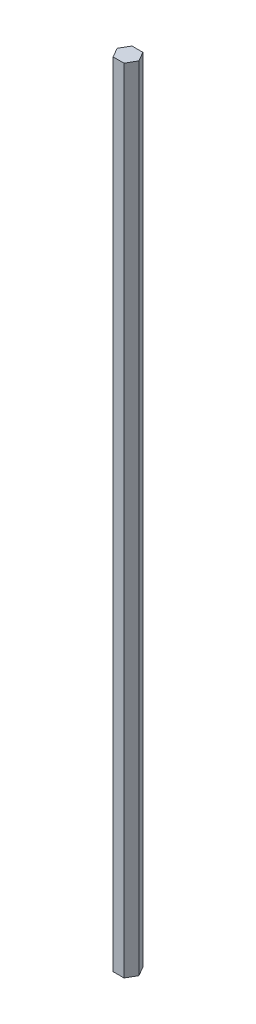
SolidWorks part; units mm, degrees
material "6061-T6 (SS)"
ref_plane "Front" through (0, 0, 0) normal (0, 0, 1) x (1, 0, 0)
ref_plane "Top" through (0, 0, 0) normal (0, 1, 0) x (1, 0, 0)
ref_plane "Right" through (0, 0, 0) normal (1, 0, 0) x (0, 0, -1)
sketch "Sketch1" plane through (0, 0, 0) normal (0, 1, 0) x (1, 0, 0)
  line L1 (7.3323, 0) -> (3.6662, 6.35)
  line L2 (3.6662, 6.35) -> (-3.6662, 6.35)
  line L3 (-3.6662, 6.35) -> (-7.3323, 0)
  line L4 (-7.3323, 0) -> (-3.6662, -6.35)
  line L5 (-3.6662, -6.35) -> (3.6662, -6.35)
  line L6 (3.6662, -6.35) -> (7.3323, 0)
  circle A0 centre (0, 0) radius 6.35 construction
  dimension "D1" = 12.7
extrude "Boss-Extrude1" add sketch "Sketch1" along normal blind 533.4
ref_axis "Axis1" through (0, 50, 0) along (0, -1, 0)
